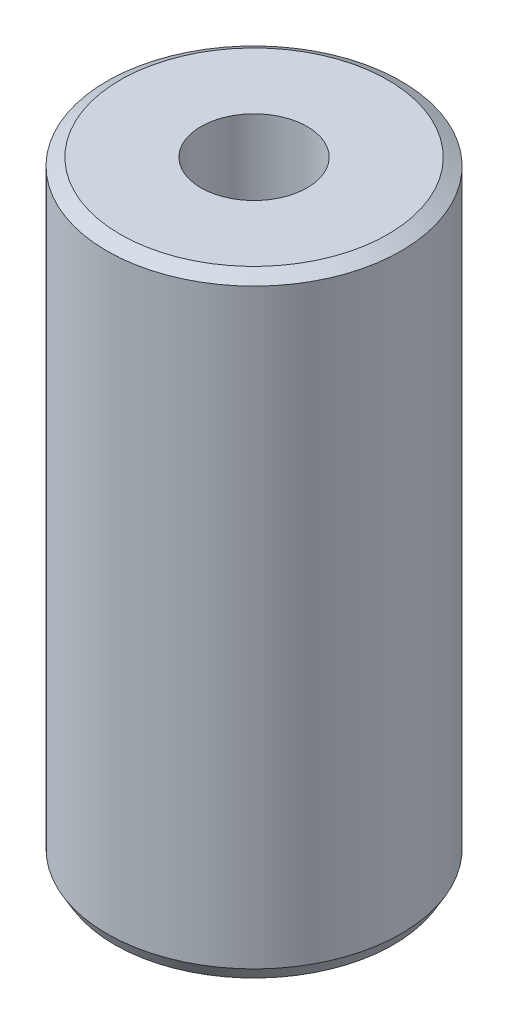
SolidWorks part; units mm, degrees
ref_plane "Front Plane" through (0, 0, 0) normal (0, 0, 1) x (1, 0, 0)
ref_plane "Top Plane" through (0, 0, 0) normal (0, 1, 0) x (1, 0, 0)
ref_plane "Right Plane" through (0, 0, 0) normal (1, 0, 0) x (0, 0, -1)
sketch "Sketch1" plane through (0, 0, 0) normal (0, 1, 0) x (1, 0, 0)
  circle A0 centre (0, 0) radius 17.5
  dimension "SHAFT_OD" = 35
extrude "Boss-Extrude1" add sketch "Sketch1" along normal blind 72.8393
sketch "Sketch2" plane through (0, 0, 0) normal (0, 1, 0) x (1, 0, 0)
  circle A0 centre (0, 0) radius 6.3222
  dimension "BORE_D" = 12.6444
extrude "Cut-Extrude1" cut sketch "Sketch2" along normal through all
chamfer "Chamfer1" distance 0.9147 angle 60 2 edges at (0, 72.8393, 17.5) (0, 0, 17.5) first distance on face at (0, 72.8393, 17.5) first distance on face at (0, 0, 6.3222)
